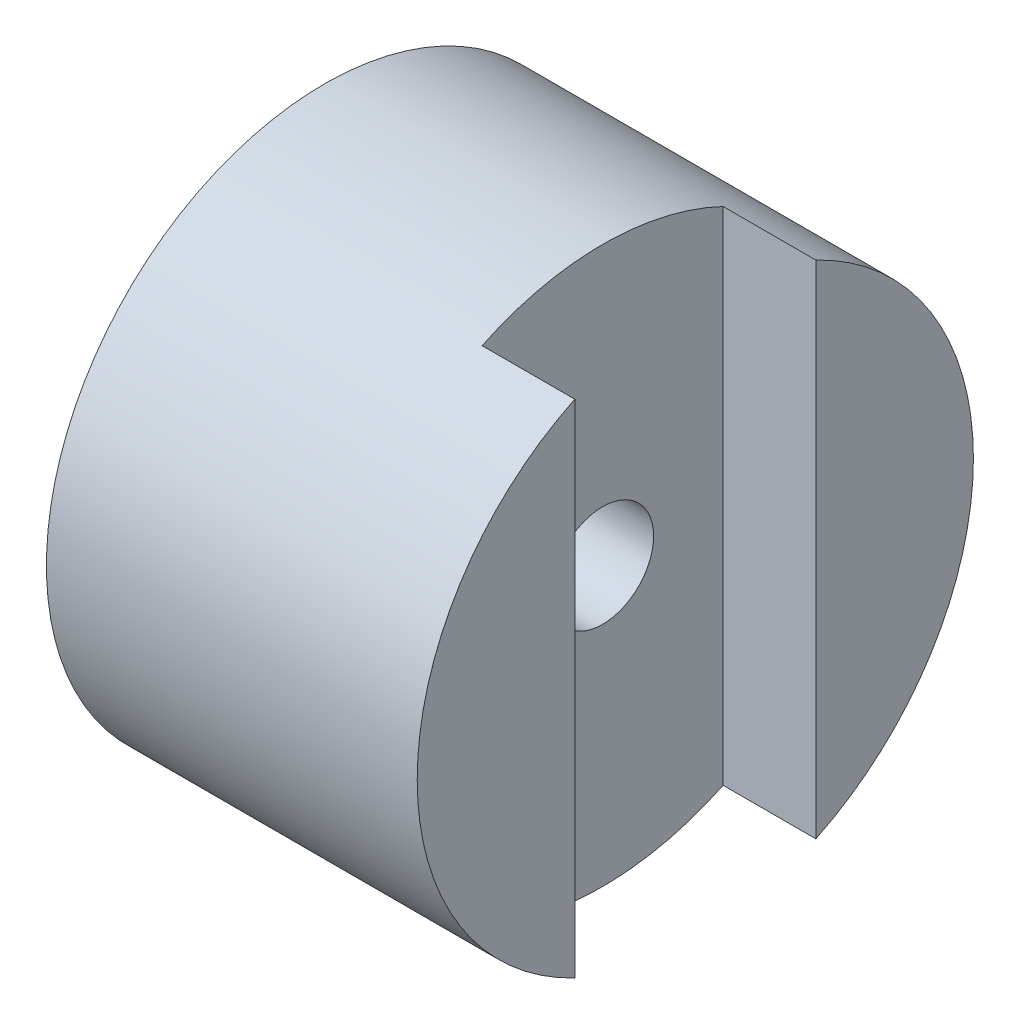
SolidWorks part; units mm, degrees
ref_plane "Front Plane" through (0, 0, 0) normal (0, 0, 1) x (1, 0, 0)
ref_plane "Top Plane" through (0, 0, 0) normal (0, 1, 0) x (1, 0, 0)
ref_plane "Right Plane" through (0, 0, 0) normal (1, 0, 0) x (0, 0, -1)
sketch "Sketch1" plane through (0, 0, 0) normal (1, 0, 0) x (0, 0, -1)
  circle A0 centre (0, 0) radius 6
  point P4 (0, 0)
  dimension "D1" = 12
extrude "Boss-Extrude1" add sketch "Sketch1" against normal blind 6
sketch "Sketch2" plane through (0, 0, 0) normal (1, 0, 0) x (0, 0, -1)
  line L0 (-2.6, 5.4074) -> (-2.6, -5.4074)
  line L1 (2.6, -5.4074) -> (2.6, 5.4074)
  line L2 (-2.6, 0) -> (2.6, 0) construction
  arc A0 (-2.6, 5.4074) -> (-2.6, -5.4074) centre (0, 0) ccw
  circle A1 centre (0, 0) radius 6 construction
  arc A2 (2.6, 5.4074) -> (2.6, -5.4074) centre (0, 0) cw
  point P10 (0, 0)
  dimension "D1" = 5.2
extrude "Boss-Extrude2" add sketch "Sketch2" along normal blind 2
hole_wizard "M2 Clearance Hole1" positions "Sketch3" profile "Sketch4" hole size "M2" standard "ANSI Metric" end condition up to next
sketch "Sketch3" plane through (0, 0, 0) normal (1, 0, 0) x (0, 0, -1)
  point P0 (0, 0)
sketch "Sketch4" plane through (0, 0, 0) normal (0, 1, 0) x (0, 0, -1)
  line L0 (0, 0) -> (0, 6)
  line L1 (0, 6) -> (1.1, 6)
  line L2 (1.1, 6) -> (1.1, 0)
  line L5 (1.1, 0) -> (0, 0)
  line L11 (0, -6.35) -> (0, 107.95) construction
  dimension "Thru Hole Dia." = 2.2
  dimension "Thru Hole Depth" = 6
